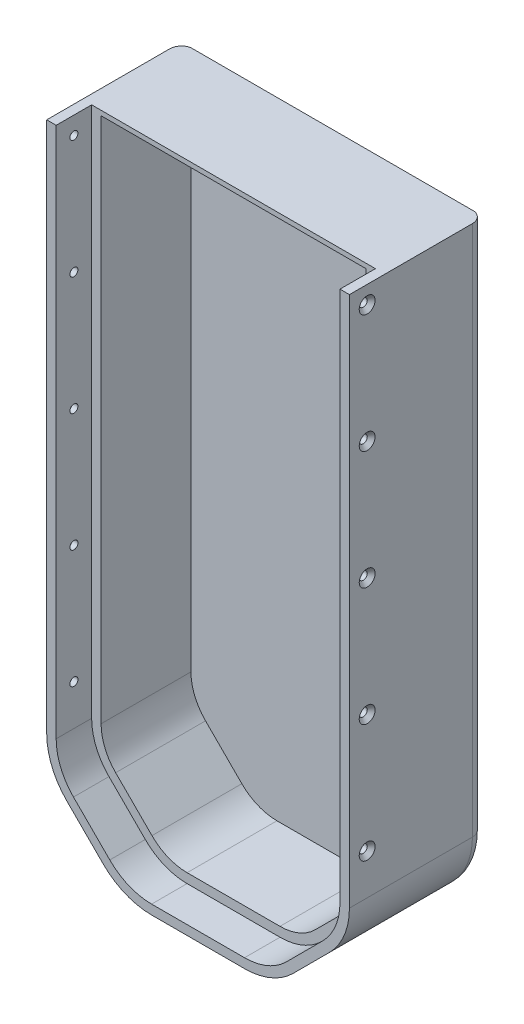
SolidWorks part; units mm, degrees
ref_plane "Front Plane" through (0, 0, 0) normal (0, 0, 1) x (1, 0, 0)
ref_plane "Top Plane" through (0, 0, 0) normal (0, 1, 0) x (1, 0, 0)
ref_plane "Right Plane" through (0, 0, 0) normal (1, 0, 0) x (0, 0, -1)
ref_axis "X" through (88.99, 0, 0) along (-1, 0, 0)
ref_axis "Y" through (0, 55, 0) along (0, -1, 0)
ref_axis "Z" through (0, 0, -88.99) along (0, 0, 1)
sketch "Sketch1" plane through (0, 0, 0) normal (0, 0, 1) x (1, 0, 0)
  line L0 (0, -50) -> (0, 0) construction
  line L1 (-60, 215) -> (60, 215)
  line L2 (-60, 215) -> (-60, -50)
  line L3 (-60, -50) -> (60, -50)
  line L4 (60, 215) -> (60, -50)
  dimension "D1" = 120
  dimension "D2" = 265
  dimension "D3" = 50
extrude "Boss-Extrude1" add sketch "Sketch1" along normal blind 42
chamfer "Chamfer1" distance 30 angle 45 2 edges at (-60, -50, 21) (60, -50, 21)
fillet "Fillet3" radius 25 4 edges at (-60, -20, 21) (-30, -50, 21) (30, -50, 21) (60, -20, 21)
fillet "Fillet1" [suppressed] radius 5
shell "Shell1" thickness 4 removed face at (0, 16.5738, 42)
fillet "Fillet4" radius 5 2 edges at (56, 211, 23) (-56, 211, 23)
sketch "Sketch2" plane through (0, 0, 42) normal (0, 0, 1) x (1, 0, 0)
  line L12 (-64, 219) -> (-64, -9.6447)
  line L13 (-55.5061, -30.1508) -> (-40.1508, -45.5061)
  line L14 (-19.6447, -54) -> (19.6447, -54)
  line L15 (40.1508, -45.5061) -> (55.5061, -30.1508)
  line L16 (64, -9.6447) -> (64, 219)
  line L17 (64, 219) -> (-64, 219)
  line L18 (-64, 219) -> (-64, -9.6447)
  line L19 (-55.5061, -30.1508) -> (-40.1508, -45.5061)
  line L20 (-19.6447, -54) -> (19.6447, -54)
  line L21 (40.1508, -45.5061) -> (55.5061, -30.1508)
  line L22 (64, -9.6447) -> (64, 219)
  line L23 (64, 219) -> (-64, 219)
  line L30 (-60, 215) -> (-60, -9.6447)
  line L31 (-52.6777, -27.3223) -> (-37.3223, -42.6777)
  line L32 (-19.6447, -50) -> (19.6447, -50)
  line L33 (37.3223, -42.6777) -> (52.6777, -27.3223)
  line L34 (60, -9.6447) -> (60, 215)
  line L35 (60, 215) -> (-60, 215)
  arc A8 (-64, -9.6447) -> (-55.5061, -30.1508) centre (-35, -9.6447) ccw
  arc A9 (-40.1508, -45.5061) -> (-19.6447, -54) centre (-19.6447, -25) ccw
  arc A10 (19.6447, -54) -> (40.1508, -45.5061) centre (19.6447, -25) ccw
  arc A11 (55.5061, -30.1508) -> (64, -9.6447) centre (35, -9.6447) ccw
  arc A12 (-64, -9.6447) -> (-55.5061, -30.1508) centre (-35, -9.6447) ccw
  arc A13 (-40.1508, -45.5061) -> (-19.6447, -54) centre (-19.6447, -25) ccw
  arc A14 (19.6447, -54) -> (40.1508, -45.5061) centre (19.6447, -25) ccw
  arc A15 (55.5061, -30.1508) -> (64, -9.6447) centre (35, -9.6447) ccw
  arc A20 (-60, -9.6447) -> (-52.6777, -27.3223) centre (-35, -9.6447) ccw
  arc A21 (-37.3223, -42.6777) -> (-19.6447, -50) centre (-19.6447, -25) ccw
  arc A22 (19.6447, -50) -> (37.3223, -42.6777) centre (19.6447, -25) ccw
  arc A23 (52.6777, -27.3223) -> (60, -9.6447) centre (35, -9.6447) ccw
  dimension "D1" = 4
  dimension "D2" = 4
extrude "Boss-Extrude2" add sketch "Sketch2" along normal blind 15 and the other way blind 42
fillet "Fillet7" radius 5 10 edges at (64, 104.6777, 0) (61.7925, -20.7425, 0) (47.8284, -37.8284, 0) (30.7425, -51.7925, 0) (0, -54, 0) (-30.7425, -51.7925, 0) (-47.8284, -37.8284, 0) (-61.7925, -20.7425, 0) (-64, 104.6777, 0) (0, 219, 0)
sketch "Sketch4" plane through (0, 0, 57) normal (0, 0, 1) x (1, 0, 0)
  line L1 (-64, 219) -> (64, 219)
  line L2 (-64, 219) -> (-64, 215)
  line L3 (-64, 215) -> (64, 215)
  line L4 (64, 219) -> (64, 215)
  line L7 (60, 215) -> (-60, 215) construction
  line L8 (64, 219) -> (-64, 219) construction
  line L9 (-64, 219) -> (-64, -9.6447) construction
  line L10 (64, -9.6447) -> (64, 219) construction
extrude "Cut-Extrude1" cut sketch "Sketch4" against normal through all
sketch "Sketch5" plane through (-64, 0, 0) normal (-1, 0, 0) x (0, 0, 1)
  line L1 (57, 215) -> (57, -9.6447) construction
  line L2 (5, 215) -> (57, 215) construction
  point P0 (49.5, 207.5)
  point P1 (49.5, 157.5)
  point P2 (49.5, 107.5)
  point P3 (49.5, 57.5)
  point P4 (49.5, 7.5)
  dimension "D1" = 50
  dimension "D2" = 7.5
  dimension "D3" = 7.5
  dimension "D4" = 50
  dimension "D5" = 50
  dimension "D6" = 50
hole_wizard "CSK for M3 SFHCS1" positions "3DSketch1" profile "Sketch6" countersink size "M3" standard "ANSI Metric"
sketch3d "3DSketch1"
  point P0 (-64, 7.5, 49.5)
  point P3 (-64, 57.5, 49.5)
  point P6 (-64, 107.5, 49.5)
  point P9 (-64, 157.5, 49.5)
  point P12 (-64, 207.5, 49.5)
sketch "Sketch6" plane through (-64, 7.5, 49.5) normal (0, 1, 0) x (0, 0, 1)
  line L0 (0, 0) -> (0, 16.0215)
  line L1 (0, 16.0215) -> (1.7, 15)
  line L2 (1.7, 15) -> (1.7, 1.66)
  line L3 (1.7, 1.66) -> (3.36, 0)
  line L5 (3.36, 0) -> (0, 0)
  line L6 (-1.7, 1.66) -> (-3.36, 0) construction
  line L10 (0, 16.0215) -> (-1.7, 15) construction
  line L11 (0, -6.35) -> (0, 107.95) construction
  dimension "Hole Dia." = 3.4
  dimension "Hole Depth" = 15
  dimension "Near C'Sink Dia." = 6.72
  dimension "Near C'Sink Angle" = 90
  dimension "Drill Angle" = 118
mirror "Mirror1" about plane through (0, 0, 0) normal (1, 0, 0) of "CSK for M3 SFHCS1"
sketch "Sketch7" plane through (0, 0, 4) normal (0, 0, 1) x (1, 0, 0)
  line L0 (56, -9.6447) -> (56, 206) construction
  line L1 (56, 192.2336) -> (-56, 192.2336)
  line L2 (56, 192.2336) -> (56, 213)
  line L3 (56, 213) -> (-56, 213)
  line L4 (-56, 192.2336) -> (-56, 213)
  line L5 (-56, 206) -> (-56, -9.6447) construction
  line L6 (60, 215) -> (-60, 215) construction
  dimension "D1" = 2
extrude "Cut-Extrude2" cut sketch "Sketch7" along normal through all
